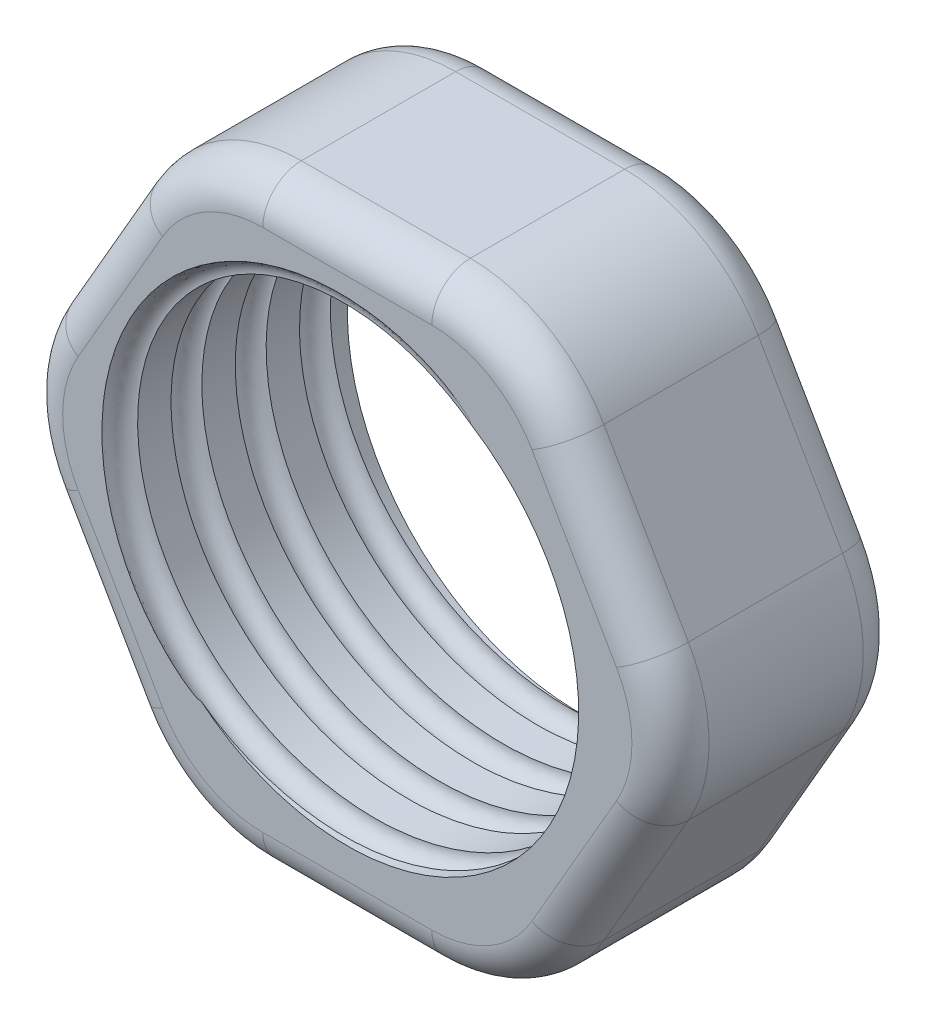
SolidWorks part; units mm, degrees
ref_plane "Front Plane" through (0, 0, 0) normal (0, 0, 1) x (1, 0, 0)
ref_plane "Top Plane" through (0, 0, 0) normal (0, 1, 0) x (1, 0, 0)
ref_plane "Right Plane" through (0, 0, 0) normal (1, 0, 0) x (0, 0, -1)
sketch "Sketch1" plane through (0, 0, 0) normal (0, 0, 1) x (1, 0, 0)
  line L41 (3.9226, 1) -> (2.8274, 2.8971)
  line L42 (1.0953, 3.8971) -> (-1.0953, 3.8971)
  line L43 (-2.8274, 2.8971) -> (-3.9226, 1)
  line L44 (-3.9226, -1) -> (-2.8274, -2.8971)
  line L45 (-1.0953, -3.8971) -> (1.0953, -3.8971)
  line L46 (2.8274, -2.8971) -> (3.9226, -1)
  circle A22 centre (0, 0) radius 3.8971 construction
  circle A23 centre (0, 0) radius 3
  arc A24 (3.9226, 1) -> (3.9226, -1) centre (2.1906, 0) cw
  arc A25 (1.0953, -3.8971) -> (2.8274, -2.8971) centre (1.0953, -1.8971) ccw
  arc A26 (-2.8274, -2.8971) -> (-1.0953, -3.8971) centre (-1.0953, -1.8971) ccw
  arc A27 (-3.9226, 1) -> (-3.9226, -1) centre (-2.1906, 0) ccw
  arc A28 (-1.0953, 3.8971) -> (-2.8274, 2.8971) centre (-1.0953, 1.8971) ccw
  arc A29 (2.8274, 2.8971) -> (1.0953, 3.8971) centre (1.0953, 1.8971) ccw
  point P12 (4.5, 0)
  point P15 (2.25, -3.8971)
  dimension "D1" = 4.5
  dimension "D2" = 6
  dimension "D3" = 2
extrude "Boss-Extrude1" add sketch "Sketch1" along normal blind 3
sketch "Sketch2" plane through (0, 0, 0) normal (0, 0, 1) x (1, 0, 0)
  circle A0 centre (0, 0) radius 3
  dimension "D1" = 6
curve "Helix/Spiral1" pitch 0.8333 height 3.9583 turns 4.75
sketch "Sketch4" plane through (0, 0, 0) normal (1, 0, 0) x (0, 0, -1)
  circle A0 centre (-0.2083, -3) radius 0.2
  dimension "D1" = 0.4
sweep "Cut-Sweep8" cut profiles "Sketch4" path "Helix/Spiral1"
fillet "Fillet1" radius 0.5 12 edges at (4.1906, 0, 0) (3.375, -1.9486, 0) (2.0953, -3.6292, 0) (0, -3.8971, 0) (-2.0953, -3.6292, 0) (-3.375, -1.9486, 0) (-4.1906, 0, 0) (-3.375, 1.9486, 0) (-2.0953, 3.6292, 0) (0, 3.8971, 0) (2.0953, 3.6292, 0) (3.375, 1.9486, 0)
fillet "Fillet6" radius 0.5 12 edges at (3.375, 1.9486, 3) (2.0953, 3.6292, 3) (0, 3.8971, 3) (-2.0953, 3.6292, 3) (-3.375, 1.9486, 3) (-4.1906, 0, 3) (-3.375, -1.9486, 3) (-2.0953, -3.6292, 3) (0, -3.8971, 3) (2.0953, -3.6292, 3) (3.375, -1.9486, 3) (4.1906, 0, 3)
